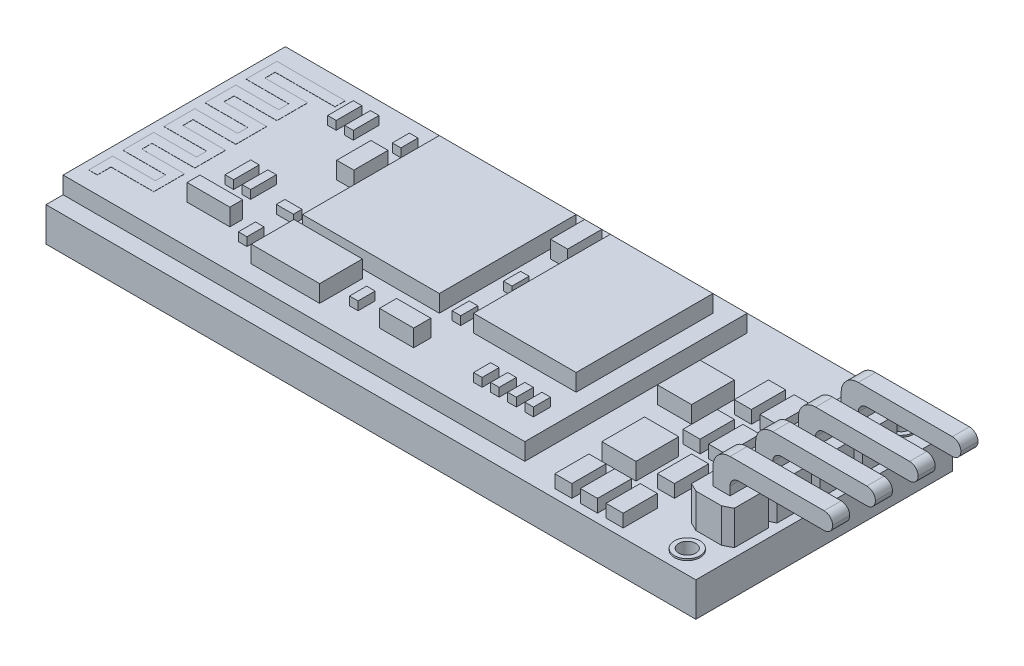
SolidWorks part; units mm, degrees
ref_plane "Alzado" through (0, 0, 0) normal (0, 0, 1) x (1, 0, 0)
ref_plane "Planta" through (0, 0, 0) normal (0, 1, 0) x (1, 0, 0)
ref_plane "Vista lateral" through (0, 0, 0) normal (1, 0, 0) x (0, 0, -1)
sketch "Croquis1" plane through (0, 0, 0) normal (0, 1, 0) x (1, 0, 0)
  line L0 (0, 0) -> (0, 7.5) construction
  line L1 (0, 0) -> (0, -7.5) construction
  line L2 (0, 0) -> (19, 0) construction
  line L3 (0, 0) -> (-19, 0) construction
  line L4 (-19, 0) -> (-19, 7.5) construction
  line L5 (-19, 7.5) -> (-19, -7.5)
  line L6 (-19, -7.5) -> (19, -7.5)
  line L7 (19, -7.5) -> (19, 7.5)
  line L8 (19, 7.5) -> (-19, 7.5)
extrude "Saliente-Extruir1" add sketch "Croquis1" along normal blind 2
sketch "Croquis2" plane through (0, 2, 0) normal (0, 1, 0) x (1, 0, 0)
  line L0 (-19, 0) -> (-19, 6.5) construction
  line L1 (-19, 7.5) -> (-19, -7.5) construction
  line L2 (-19, 6.5) -> (-19, -6.5)
  line L3 (-19, 6.5) -> (8, 6.5)
  line L4 (8, 6.5) -> (8, -6.5)
  line L5 (8, -6.5) -> (-19, -6.5)
extrude "Saliente-Extruir2" add sketch "Croquis2" along normal blind 1
sketch "Croquis3" plane through (0, 2, 0) normal (0, 1, 0) x (1, 0, 0)
  line L0 (19, 0) -> (18.5, 0) construction
  line L1 (19, -7.5) -> (19, 7.5) construction
  line L2 (18.5, 0) -> (18.5, 5)
  line L3 (18.5, 5) -> (16, 5)
  line L4 (16, 5) -> (16, -5)
  line L5 (16, -5) -> (18.5, -5)
  line L6 (18.5, -5) -> (18.5, 0)
  line L7 (18.5, 0) -> (18.52, -0.0603)
extrude "Saliente-Extruir3" add sketch "Croquis3" along normal blind 2 contours L5 L6 L2 L3 L4 region at (17.25, 2, 0)
sketch "Croquis4" plane through (0, 4, 0) normal (0, 1, 0) x (1, 0, 0)
  line L0 (16, 0) -> (16.5, 0) construction
  line L1 (18.5, 0) -> (18, 0) construction
  line L2 (18.5, 5) -> (18.5, 2.5) construction
  line L3 (18.5, 2.5) -> (16, 2.5) construction
  line L4 (16, -5) -> (18.5, -5)
  line L5 (18.5, -5) -> (18.5, 5)
  line L6 (18.5, 5) -> (16, 5)
  line L7 (16, 5) -> (16, -5)
  line L8 (16, -5) -> (18.5, -5)
  line L9 (18.5, -5) -> (18.5, 5)
  line L10 (18.5, 5) -> (16, 5)
  line L11 (16, 5) -> (16, -5)
  line L12 (18.5, -2.5) -> (16, -2.5) construction
  line L13 (16.5, 0) -> (18, 0)
  line L14 (16.5, -2.5) -> (16.5, 2.5) construction
  line L15 (16.5, 2.5) -> (16.5, 5) construction
  line L16 (18, -2.5) -> (18, 2.5) construction
  line L17 (18, 2.5) -> (18, 5) construction
  line L18 (18, -2.5) -> (18, -5) construction
  line L19 (16.5, -2.5) -> (16.5, -5) construction
  line L20 (16.5, 3.75) -> (18, 3.75) construction
  line L21 (17.25, 3.75) -> (17.25, 2.75) construction
  line L22 (17.25, 2.75) -> (18, 2.75) construction
  line L23 (17.25, 2.75) -> (16.5, 2.75) construction
  line L24 (17.25, 4.75) -> (18, 4.75) construction
  line L25 (17.25, 4.75) -> (16.5, 4.75) construction
  line L26 (17.25, 2.25) -> (18, 2.25) construction
  line L27 (17.25, 2.25) -> (16.5, 2.25) construction
  line L28 (17.25, 0.25) -> (18, 0.25) construction
  line L29 (17.25, 0.25) -> (16.5, 0.25) construction
  line L30 (17.25, -4.75) -> (16.5, -4.75) construction
  line L31 (17.25, -4.75) -> (18, -4.75) construction
  line L32 (17.25, -2.75) -> (18, -2.75) construction
  line L33 (17.25, -2.75) -> (16.5, -2.75) construction
  line L34 (17.25, -2.25) -> (16.5, -2.25) construction
  line L35 (17.25, -2.25) -> (18, -2.25) construction
  line L36 (17.25, -0.25) -> (18, -0.25) construction
  line L37 (17.25, -0.25) -> (16.5, -0.25) construction
  line L38 (16.5, -4.75) -> (16, -4.75) construction
  line L39 (16.5, -2.75) -> (16, -2.75) construction
  line L40 (18, -2.75) -> (18.5, -2.75) construction
  line L41 (18, -4.75) -> (18.5, -4.75) construction
  line L42 (16, -2.75) -> (16.5, -2.5)
  line L43 (18, -2.5) -> (16.5, -2.5)
  line L44 (18, -2.5) -> (18.5, -2.75)
  line L45 (18.5, -4.75) -> (18, -5)
  line L46 (16, -4.75) -> (16.5, -5)
  line L47 (16, -2.25) -> (16.5, -2.5)
  line L48 (18, -2.5) -> (18.5, -2.25)
  line L49 (18.5, -0.25) -> (18, 0)
  line L50 (16, -0.25) -> (16.5, 0)
  line L51 (16, 0.25) -> (16.5, 0)
  line L52 (18.5, 0.25) -> (18, 0)
  line L53 (18, 2.5) -> (18.5, 2.25)
  line L54 (16, 2.25) -> (16.5, 2.5)
  line L55 (16, 2.75) -> (16.5, 2.5)
  line L56 (18, 2.5) -> (16.5, 2.5)
  line L57 (18, 2.5) -> (18.5, 2.75)
  line L58 (18.5, 4.75) -> (18, 5)
  line L59 (16, 4.75) -> (16.5, 5)
  line M6 (16, -5) -> (18.5, -5)
  line M7 (18.5, -5) -> (18.5, 5)
  line M8 (18.5, 5) -> (16, 5)
  line M9 (16, 5) -> (16, -5)
  dimension "D1" = 0
extrude "Cortar-Extruir1" cut sketch "Croquis4" against normal blind 2 contours L59 M9 M8 | L58 L9 M8 | L57 L53 L9 | L55 L11 L54 | L9 L52 L49 | L51 L11 L50 | L48 L44 L9 | L47 L11 L42 | L45 L8 M7 | L46 M9 M6 region at (16.1667, 4, 4.9167) region at (18.3333, 4, 4.9167) region at (16.1667, 4, 2.5) region at (18.3333, 4, 2.5) region at (16.1667, 4, 0) region at (18.3333, 4, 0) region at (16.1667, 4, -2.5) region at (18.3333, 4, -2.5) region at (16.1667, 4, -4.9167) region at (18.3333, 4, -4.9167)
sketch "Croquis5" plane through (0, 2, 0) normal (0, 1, 0) x (1, 0, 0)
  line L0 (16, 0.25) -> (16, -0.25) construction
  line L1 (16, 0) -> (15, 0) construction
  line L2 (15, 0) -> (15, -7) construction
  line L3 (10, -7) -> (12.5, -7) construction
  line L4 (10, -7) -> (10, 6) construction
  line L5 (10, 6) -> (12.5, 6) construction
  line L6 (15, 6) -> (15, 0) construction
  line L7 (13.25, 0) -> (13, 0) construction
  line L8 (12.5, -7) -> (15, -7) construction
  line L9 (12.5, 6) -> (15, 6) construction
  line L10 (13.75, -7) -> (14.25, -7) construction
  line L11 (13.75, -7) -> (13.25, -7) construction
  line L12 (13.25, -7) -> (14.25, -7)
  line L13 (14.25, -7) -> (14.25, -5)
  line L14 (14.25, -5) -> (13.25, -5)
  line L15 (13.25, -5) -> (13.25, -7)
  line L16 (13.75, -5) -> (13.75, -4) construction
  line L17 (13.75, -4) -> (14.25, -4)
  line L18 (14.25, -4) -> (14.25, -2)
  line L19 (14.25, -2) -> (13.25, -2)
  line L20 (13.25, -2) -> (13.25, -4)
  line L21 (13.25, -4) -> (13.75, -4)
  line L22 (13.75, -2) -> (13.75, -1) construction
  line L23 (13.75, -1) -> (14.25, -1)
  line L24 (14.25, -1) -> (14.25, 1)
  line L25 (14.25, 1) -> (13.25, 1)
  line L26 (13.25, 1) -> (13.25, -1)
  line L27 (13.25, -1) -> (13.75, -1)
  line L28 (13.75, 1) -> (13.75, 2) construction
  line L29 (13.75, 2) -> (14.25, 2)
  line L30 (14.25, 2) -> (14.25, 4)
  line L31 (14.25, 4) -> (13.25, 4)
  line L32 (13.25, 4) -> (13.25, 2)
  line L33 (13.25, 2) -> (13.75, 2)
  line L34 (13, 0) -> (13, -7) construction
  line L35 (13, 0) -> (13, 6) construction
  line L36 (12.75, 4) -> (12.75, 2)
  line L37 (12.75, 2) -> (12.25, 2)
  line L38 (12.25, 2) -> (11.75, 2)
  line L39 (11.75, 2) -> (11.75, 4)
  line L40 (11.75, 4) -> (12.75, 4)
  line L41 (12.25, -1) -> (11.75, -1)
  line L42 (12.75, -1) -> (12.25, -1)
  line L43 (12.75, 1) -> (12.75, -1)
  line L44 (11.75, 1) -> (12.75, 1)
  line L45 (11.75, -1) -> (11.75, 1)
  line L46 (12.75, -5) -> (12.75, -7)
  line L47 (11.75, -5) -> (12.75, -5)
  line L48 (11.75, -7) -> (11.75, -5)
  line L49 (12.75, -7) -> (11.75, -7)
  line L50 (11.75, 0) -> (11.5, 0) construction
  line L51 (11.5, 0) -> (11.5, -7) construction
  line L52 (11.25, -7) -> (11.25, -5)
  line L53 (11.25, -5) -> (10.25, -5)
  line L54 (10.25, -5) -> (10.25, -7)
  line L55 (10.25, -7) -> (11.25, -7)
  line L56 (13.25, -3) -> (12.25, -3) construction
  line L57 (12.25, -3) -> (12.25, -4.25)
  line L58 (12.25, -4.25) -> (10.25, -4.25)
  line L59 (10.25, -4.25) -> (10.25, -1.75)
  line L60 (10.25, -1.75) -> (12.25, -1.75)
  line L61 (12.25, -1.75) -> (12.25, -3)
  line L62 (12.25, 2) -> (12.25, 1) construction
  line L63 (12.25, 1.5) -> (11, 1.5) construction
  line L64 (11, 1.5) -> (11, 0.25)
  line L65 (11, 1.5) -> (11, 2.75)
  line L66 (11, 0.25) -> (9, 0.25)
  line L67 (9, 0.25) -> (9, 2.75)
  line L68 (9, 2.75) -> (11, 2.75)
extrude "Saliente-Extruir4" add sketch "Croquis5" along normal blind 0.75
sketch "Croquis6" plane through (0, 2.75, 0) normal (0, 1, 0) x (1, 0, 0)
  line L4 (12.25, -4.25) -> (12.25, -1.75)
  line L5 (12.25, -1.75) -> (10.25, -1.75)
  line L6 (10.25, -1.75) -> (10.25, -4.25)
  line L7 (10.25, -4.25) -> (12.25, -4.25)
  line L8 (12.25, -4.25) -> (12.25, -1.75)
  line L9 (12.25, -1.75) -> (10.25, -1.75)
  line L10 (10.25, -1.75) -> (10.25, -4.25)
  line L11 (10.25, -4.25) -> (12.25, -4.25)
  dimension "D1" = 0
extrude "Saliente-Extruir5" add sketch "Croquis6" along normal blind 0.25
sketch "Croquis7" plane through (0, 2.75, 0) normal (0, 1, 0) x (1, 0, 0)
  line L4 (11, 0.25) -> (11, 2.75)
  line L5 (11, 2.75) -> (9, 2.75)
  line L6 (9, 2.75) -> (9, 0.25)
  line L7 (9, 0.25) -> (11, 0.25)
  line L8 (11, 0.25) -> (11, 2.75)
  line L9 (11, 2.75) -> (9, 2.75)
  line L10 (9, 2.75) -> (9, 0.25)
  line L11 (9, 0.25) -> (11, 0.25)
  dimension "D1" = 0
extrude "Saliente-Extruir6" add sketch "Croquis7" along normal blind 0.25
sketch "Croquis8" plane through (0, 4, 0) normal (0, 1, 0) x (1, 0, 0)
  line L0 (17.25, 2.5) -> (17.25, 5) construction
  line L2 (17.25, 0) -> (17.25, 2.5) construction
  line L3 (18, 5) -> (16.5, 5) construction
  line L4 (17.25, 0) -> (18, 0) construction
  line L5 (16.5, -2.5) -> (18, -2.5) construction
  line L6 (17.75, -4.25) -> (16.75, -4.25)
  line L7 (17.75, -4.25) -> (17.75, -3.25)
  line L8 (17.75, -3.25) -> (16.75, -3.25)
  line L9 (16.75, -4.25) -> (16.75, -3.25)
  line L10 (17.75, -4.25) -> (16.75, -3.25) construction
  line L11 (17.75, -3.25) -> (16.75, -4.25) construction
  line L12 (17.75, -0.75) -> (16.75, -0.75)
  line L13 (16.75, -0.75) -> (16.75, -1.75)
  line L14 (17.75, -1.75) -> (16.75, -1.75)
  line L15 (17.75, -0.75) -> (17.75, -1.75)
  line L16 (17.75, 1.75) -> (16.75, 1.75)
  line L17 (16.75, 0.75) -> (16.75, 1.75)
  line L18 (17.75, 0.75) -> (16.75, 0.75)
  line L19 (17.75, 0.75) -> (17.75, 1.75)
  line L20 (17.75, 4.25) -> (16.75, 4.25)
  line L21 (16.75, 4.25) -> (16.75, 3.25)
  line L22 (17.75, 3.25) -> (16.75, 3.25)
  line L23 (17.75, 4.25) -> (17.75, 3.25)
  circle A0 centre (17.25, 3.75) radius 0.5 construction
  circle A1 centre (17.25, 1.25) radius 0.5 construction
  circle A2 centre (17.25, -3.75) radius 0.5 construction
  circle A3 centre (17.25, -1.25) radius 0.5 construction
extrude "Saliente-Extruir8" add sketch "Croquis8" along normal blind 2
sketch "Croquis9" plane through (16.75, 0, 0) normal (-1, 0, 0) x (0, 0, 1)
  line L0 (3.25, 6) -> (4.25, 6)
  line L1 (4.25, 6) -> (4.25, 5)
  line L2 (4.25, 6) -> (4.25, 4) construction
  line L3 (4.25, 5) -> (3.25, 5)
  line L4 (3.25, 6) -> (3.25, 4) construction
  line L5 (3.25, 5) -> (3.25, 6)
  line L6 (1.75, 6) -> (1.75, 5)
  line L7 (1.75, 6) -> (1.75, 4) construction
  line L8 (1.75, 5) -> (0.75, 5)
  line L9 (0.75, 6) -> (0.75, 4) construction
  line L10 (0.75, 5) -> (0.75, 6)
  line L11 (0.75, 6) -> (1.75, 6)
  line L12 (-1.75, 6) -> (-0.75, 6)
  line L13 (-0.75, 6) -> (-0.75, 5)
  line L14 (-0.75, 6) -> (-0.75, 4) construction
  line L15 (-0.75, 5) -> (-1.75, 5)
  line L16 (-1.75, 6) -> (-1.75, 4) construction
  line L17 (-1.75, 5) -> (-1.75, 6)
  line L18 (-3.25, 6) -> (-3.25, 5)
  line L19 (-3.25, 6) -> (-3.25, 4) construction
  line L20 (-3.25, 5) -> (-4.25, 5)
  line L21 (-4.25, 6) -> (-4.25, 4) construction
  line L22 (-4.25, 5) -> (-4.25, 6)
  line L23 (-4.25, 6) -> (-3.25, 6)
extrude "Saliente-Extruir9" add sketch "Croquis9" against normal blind 7
fillet "Redondeo1" radius 0.5 1 edges at (17.75, 5, 3.75) type face fillet first side face at (17.75, 4.5, 3.75) second side face at (20.75, 5, 3.75)
fillet "Redondeo2" radius 0.5 1 edges at (17.75, 5, 1.25) type face fillet first side face at (17.75, 4.5, 1.25) second side face at (20.75, 5, 1.25)
fillet "Redondeo3" radius 0.5 1 edges at (17.75, 5, -1.25) type face fillet first side face at (17.75, 4.5, -1.25) second side face at (20.75, 5, -1.25)
fillet "Redondeo4" radius 0.5 1 edges at (17.75, 5, -3.75) type face fillet first side face at (17.75, 4.5, -3.75) second side face at (20.75, 5, -3.75)
fillet "Redondeo5" radius 1 1 edges at (16.75, 6, 3.75) type face fillet first side face at (16.75, 5, 3.75) second side face at (20.25, 6, 3.75)
fillet "Redondeo6" radius 1 1 edges at (16.75, 6, 1.25) type face fillet first side face at (16.75, 5, 1.25) second side face at (20.25, 6, 1.25)
fillet "Redondeo7" radius 1 1 edges at (16.75, 6, -1.25) type face fillet first side face at (16.75, 5, -1.25) second side face at (20.25, 6, -1.25)
fillet "Redondeo8" radius 1 1 edges at (16.75, 6, -3.75) type face fillet first side face at (16.75, 5, -3.75) second side face at (20.25, 6, -3.75)
sketch "Croquis10" plane through (0, 2, 0) normal (0, 1, 0) x (1, 0, 0)
  line L0 (17.25, -5) -> (17.25, -7.5) construction
  line L1 (16.5, -5) -> (18, -5) construction
  line L2 (-19, -7.5) -> (19, -7.5) construction
  line L3 (17.25, 5) -> (17.25, 7.5) construction
  line L4 (18, 5) -> (16.5, 5) construction
  line L5 (19, 7.5) -> (-19, 7.5) construction
  circle A0 centre (17.25, -6.25) radius 0.5
  circle A1 centre (17.25, 6.25) radius 0.5
  circle A2 centre (17.25, -6.25) radius 0.75
  circle A3 centre (17.25, 6.25) radius 0.75
extrude "Saliente-Extruir10" add sketch "Croquis10" along normal blind 0.1 and the other way blind 2.1
sketch "Croquis11" plane through (0, 2, 0) normal (0, 1, 0) x (1, 0, 0)
  circle A1 centre (17.25, 6.25) radius 0.5
  circle A2 centre (17.25, 6.25) radius 0.5
  dimension "D1" = 0
extrude "Cortar-Extruir2" cut sketch "Croquis11" against normal blind 2
sketch "Croquis12" plane through (0, 2, 0) normal (0, 1, 0) x (1, 0, 0)
  circle A1 centre (17.25, -6.25) radius 0.5
  circle A2 centre (17.25, -6.25) radius 0.5
  dimension "D1" = 0
extrude "Cortar-Extruir3" cut sketch "Croquis12" against normal blind 2
sketch "Croquis13" plane through (0, 3, 0) normal (0, 1, 0) x (1, 0, 0)
  line L3 (-9, 5.5) -> (-9, -2.5)
  line L4 (-9, -2.5) -> (-1, -2.5)
  line L5 (-1, -2.5) -> (-1, 5.5)
  line L6 (-1, 5.5) -> (-9, 5.5)
  line L7 (0, -4) -> (0, -5)
  line L8 (1, 1.5) -> (1, 5.5)
  line L9 (1, 5.5) -> (7, 5.5)
  line L10 (7, 5.5) -> (7, -2.5)
  line L11 (7, -2.5) -> (1, -2.5)
  line L12 (1, -2.5) -> (1, 1.5)
  line L19 (0, -5) -> (-2, -5)
  line L20 (-2, -5) -> (-2, -4)
  line L21 (-2, -4) -> (0, -4)
extrude "Saliente-Extruir11" add sketch "Croquis13" along normal blind 1
sketch "Croquis14" plane through (0, 3, 0) normal (0, 1, 0) x (1, 0, 0)
  line L0 (-19, 0) -> (-18.5, 0) construction
  line L1 (-19, 6.5) -> (-19, -6.5) construction
  line L2 (-18.5, 0) -> (-18.5, 6.5) construction
  line L3 (8, 6.5) -> (-19, 6.5) construction
  line L4 (-18.5, 0) -> (-18.5, -6.5) construction
  line L5 (-19, -6.5) -> (8, -6.5) construction
  line L6 (-19, 6.5) -> (-19, 5.5) construction
  line L7 (-19, 5.5) -> (-18.5, 5.5) construction
  line L8 (-18.5, 5.5) -> (-14.5, 5.5)
  line L9 (-14.5, 5.5) -> (-14.5, 4.9)
  line L10 (-14.5, 4.9) -> (-18, 4.9)
  line L11 (-18, 4.9) -> (-18, 4.3)
  line L12 (-18, 4.3) -> (-15.5, 4.3)
  line L13 (-15.5, 4.3) -> (-15.5, 2.5)
  line L14 (-15.5, 2.5) -> (-18, 2.5)
  line L15 (-18, 2.5) -> (-18, 1.9)
  line L16 (-18, 1.9) -> (-15.5, 1.9)
  line L17 (-15.5, 1.9) -> (-15.5, 0.1)
  line L18 (-18.5, 5.5) -> (-18.5, 3.7)
  line L19 (-18.5, 3.7) -> (-16, 3.7)
  line L20 (-16, 3.7) -> (-16, 3.1)
  line L21 (-16, 3.1) -> (-18.5, 3.1)
  line L22 (-18.5, 3.1) -> (-18.5, 1.3)
  line L23 (-18.5, 1.3) -> (-16, 1.3)
  line L24 (-16, 0.7) -> (-18.5, 0.7)
  line L25 (-16, 1.3) -> (-16, 0.7)
  line L26 (-18.5, 0.7) -> (-18.5, -1.1)
  line L27 (-15.5, 0.1) -> (-18, 0.1)
  line L28 (-18, 0.1) -> (-18, -0.5)
  line L29 (-18, -0.5) -> (-15.5, -0.5)
  line L30 (-15.5, -0.5) -> (-15.5, -2.3)
  line L31 (-18.5, -1.1) -> (-16, -1.1)
  line L32 (-16, -1.1) -> (-16, -1.7)
  line L33 (-16, -1.7) -> (-18.5, -1.7)
  line L34 (-15.5, -2.3) -> (-18, -2.3)
  line L35 (-18, -2.3) -> (-18, -2.9)
  line L36 (-18, -2.9) -> (-15.5, -2.9)
  line L37 (-18.5, -1.7) -> (-18.5, -3.5)
  line L38 (-18.5, -3.5) -> (-16, -3.5)
  line L39 (-16, -3.5) -> (-16, -4.1)
  line L40 (-18.5, -6.5) -> (-18.5, -5.5) construction
  line L41 (-15.5, -2.9) -> (-15.5, -4.7)
  line L42 (-15.5, -4.7) -> (-18, -4.7)
  line L43 (-18, -4.7) -> (-18, -5.5)
  line L44 (-16, -4.1) -> (-18.5, -4.1)
  line L45 (-18.5, -4.1) -> (-18.5, -5.5)
  line L46 (-18, -5.5) -> (-18.5, -5.5)
extrude "Saliente-Extruir12" add sketch "Croquis14" along normal blind 0.01
sketch "Croquis15" plane through (0, 3, 0) normal (0, 1, 0) x (1, 0, 0)
  line L0 (-10.25, 4.25) -> (-10.25, 3.25) construction
  line L1 (-10.25, -2.25) -> (-9.7803, -2.25) construction
  line L2 (7, -4) -> (7, -5)
  line L3 (7, -5) -> (7.0244, -5.0141)
  line L4 (7, -4) -> (6.5, -4)
  line L5 (6.5, -4) -> (6.5, -5)
  line L6 (6.5, -5) -> (7, -5)
  line L7 (-9.7803, -2.25) -> (-10.7803, -2.25)
  line L8 (-1, -2.5) -> (1, -2.5) construction
  line L9 (-10.7803, -2.25) -> (-10.7803, -1.75)
  line L10 (5.5, -4) -> (6, -4)
  line L11 (5.5, -4) -> (5.5, -5)
  line L12 (6, -5) -> (5.5, -5)
  line L13 (6, -4) -> (6, -5)
  line L14 (0, -1.5) -> (0.25, -1.5) construction
  line L15 (0.25, -1.5) -> (-0.25, -1.5)
  line L16 (5, -4) -> (5, -5)
  line L17 (5, -4) -> (4.5, -4)
  line L18 (4.5, -4) -> (4.5, -5)
  line L19 (4.5, -5) -> (5, -5)
  line L20 (4, -5) -> (3.5, -5)
  line L21 (4, -4) -> (4, -5)
  line L22 (3.5, -4) -> (4, -4)
  line L23 (3.5, -4) -> (3.5, -5)
  line L24 (-0.25, -1.5) -> (-0.25, -2.5)
  line L25 (-0.25, -2.5) -> (0.25, -2.5)
  line L26 (0.25, -2.5) -> (0.25, -1.5)
  line L27 (0, 1.5) -> (0, 3.5) construction
  line L28 (0, 3.5) -> (0.5, 3.5)
  line L29 (-0.25, 1.5) -> (0.25, 1.5)
  line L30 (-0.25, 0.5) -> (-0.25, 1.5)
  line L31 (0.25, 0.5) -> (-0.25, 0.5)
  line L32 (0.25, 1.5) -> (0.25, 0.5)
  line L33 (0.5, 3.5) -> (0.5, 5.5)
  line L34 (0.5, 5.5) -> (-0.5, 5.5)
  line L35 (-0.5, 5.5) -> (-0.5, 3.5)
  line L36 (-0.5, 3.5) -> (0, 3.5)
  line L37 (-9, -2.5) -> (-9, -6.5) construction
  line L38 (-19, -6.5) -> (8, -6.5) construction
  line L39 (-5, -2.5) -> (-5, -3) construction
  line L40 (-9, -2.5) -> (-1, -2.5) construction
  line L41 (-5, -3) -> (-5, -5.5)
  line L42 (-5, -3) -> (-9, -3)
  line L43 (-9, -3) -> (-9, -5.5)
  line L44 (-9, -5.5) -> (-5, -5.5)
  line L45 (-10.7803, -1.75) -> (-9.7803, -1.75)
  line L46 (-4, -4.25) -> (-4, -4.75) construction
  line L47 (-4, -4.75) -> (-4, -3.75)
  line L48 (-4, -3.75) -> (-3.5, -3.75)
  line L49 (-3.5, -3.75) -> (-3.5, -4.75)
  line L50 (-3.5, -4.75) -> (-4, -4.75)
  line L51 (-7, -3) -> (-7, -5.5) construction
  line L52 (-10.5, -4.75) -> (-10, -4.75)
  line L53 (-10, -4.75) -> (-10, -3.75)
  line L54 (-10, -3.75) -> (-10.5, -3.75)
  line L55 (-10.5, -3.75) -> (-10.5, -4.75)
  line L56 (-12.2803, -2.25) -> (-12.2803, -0.75)
  line L57 (-9.7803, -1.75) -> (-9.7803, -2.25)
  line L58 (-12.2803, -0.75) -> (-12.7803, -0.75)
  line L59 (-12.7803, -0.75) -> (-12.7803, -2.25)
  line L60 (-12.7803, -2.25) -> (-12.2803, -2.25)
  line L61 (-13.7803, 5.25) -> (-13.2803, 5.25)
  line L62 (-13.2803, -2.25) -> (-13.2803, -0.75)
  line L63 (-13.2803, -0.75) -> (-13.7803, -0.75)
  line L64 (-13.7803, -0.75) -> (-13.7803, -2.25)
  line L65 (-13.7803, -2.25) -> (-13.2803, -2.25)
  line L66 (-13.7803, 3.75) -> (-13.7803, 5.25)
  line L68 (-10.25, 3.25) -> (-9.75, 3.25)
  line L69 (-13.2803, 3.75) -> (-13.7803, 3.75)
  line L70 (-13.2803, 5.25) -> (-13.2803, 3.75)
  line L71 (-12.7803, 5.25) -> (-12.2803, 5.25)
  line L72 (-12.7803, 3.75) -> (-12.7803, 5.25)
  line L73 (-12.2803, 3.75) -> (-12.7803, 3.75)
  line L74 (-12.2803, 5.25) -> (-12.2803, 3.75)
  line L75 (-9.75, 3.25) -> (-9.75, 1.25)
  line L76 (-9.75, 1.25) -> (-10.75, 1.25)
  line L77 (-10.5, 4.25) -> (-10.5, 5.25)
  line L78 (-10, 4.25) -> (-10.5, 4.25)
  line L79 (-10, 5.25) -> (-10, 4.25)
  line L80 (-10.5, 5.25) -> (-10, 5.25)
  line L81 (-10.75, 1.25) -> (-10.75, 3.25)
  line L82 (-10.75, 3.25) -> (-10.25, 3.25)
extrude "Saliente-Extruir13" add sketch "Croquis15" along normal blind 0.5 contours L59 L60 L56 L58 | L57 L45 L9 L7 | L82 L81 L76 L75 L68 | L43 L44 L41 L42 | L50 L49 L48 L47 | L25 L26 L15 L24 | L32 L29 L30 L31 | L35 L36 L28 L33 L34 | L22 L23 L20 L21 | L18 L19 L16 L17 | L13 L10 L11 L12 | L5 L6 L2 L4 | L66 L61 L70 L69 | L74 L73 L72 L71 | L77 L80 L79 L78 | L62 L63 L64 L65 | L53 L54 L55 L52 region at (6.75, 3, 4.5) region at (-10.2803, 3, 2) region at (5.75, 3, 4.5) region at (0, 3, 2) region at (4.75, 3, 4.5) region at (3.75, 3, 4.5) region at (0, 3, -4.5) region at (0, 3, -1) region at (-7, 3, 4.25) region at (-3.75, 3, 4.25) region at (-12.5303, 3, 1.5) region at (-10.25, 3, -2.25)
sketch "Croquis17" plane through (0, 3, 0) normal (0, 1, 0) x (1, 0, 0)
  line L0 (-10.5, -4.25) -> (-11.5, -4.25) construction
  line L1 (-10.5, -3.75) -> (-10.5, -4.75) construction
  line L2 (-11.5, -4.25) -> (-11.5, -3.5)
  line L3 (-11.5, -3.5) -> (-14, -3.5)
  line L4 (-14, -3.5) -> (-14, -4.25)
  line L5 (-14, -4.25) -> (-11.5, -4.25)
extrude "Saliente-Extruir14" add sketch "Croquis17" along normal blind 1
sketch "Croquis18" plane through (0, 3.5, 0) normal (0, 1, 0) x (1, 0, 0)
  line L4 (-9.75, 3.25) -> (-10.75, 3.25)
  line L5 (-10.75, 3.25) -> (-10.75, 1.25)
  line L6 (-10.75, 1.25) -> (-9.75, 1.25)
  line L7 (-9.75, 1.25) -> (-9.75, 3.25)
  line L8 (-9.75, 3.25) -> (-10.75, 3.25)
  line L9 (-10.75, 3.25) -> (-10.75, 1.25)
  line L10 (-10.75, 1.25) -> (-9.75, 1.25)
  line L11 (-9.75, 1.25) -> (-9.75, 3.25)
  dimension "D1" = 0
extrude "Saliente-Extruir15" add sketch "Croquis18" along normal blind 0.5
sketch "Croquis19" plane through (0, 3.5, 0) normal (0, 1, 0) x (1, 0, 0)
  line L4 (-9, -3) -> (-9, -5.5)
  line L5 (-9, -5.5) -> (-5, -5.5)
  line L6 (-5, -5.5) -> (-5, -3)
  line L7 (-5, -3) -> (-9, -3)
  line L8 (-9, -3) -> (-9, -5.5)
  line L9 (-9, -5.5) -> (-5, -5.5)
  line L10 (-5, -5.5) -> (-5, -3)
  line L11 (-5, -3) -> (-9, -3)
  dimension "D1" = 0
extrude "Saliente-Extruir16" add sketch "Croquis19" along normal blind 0.5
sketch "Croquis21" plane through (0, 3.5, 0) normal (0, 1, 0) x (1, 0, 0)
  line L4 (-0.5, 5.5) -> (-0.5, 3.5)
  line L5 (-0.5, 3.5) -> (0.5, 3.5)
  line L6 (0.5, 3.5) -> (0.5, 5.5)
  line L7 (0.5, 5.5) -> (-0.5, 5.5)
  line L8 (-0.5, 5.5) -> (-0.5, 3.5)
  line L9 (-0.5, 3.5) -> (0.5, 3.5)
  line L10 (0.5, 3.5) -> (0.5, 5.5)
  line L11 (0.5, 5.5) -> (-0.5, 5.5)
  dimension "D1" = 0
extrude "Saliente-Extruir17" add sketch "Croquis21" along normal blind 0.5
fillet "Redondeo9" radius 0.5 1 edges at (23.75, 6, 3.75) type face fillet first side face at (20.75, 6, 3.75) second side face at (23.75, 5.5, 3.75)
fillet "Redondeo12" radius 0.5 1 edges at (23.75, 5, 3.75) type face fillet first side face at (23.75, 5.25, 3.75) second side face at (21, 5, 3.75)
fillet "Redondeo13" radius 0.5 1 edges at (23.75, 6, 1.25) type face fillet first side face at (20.75, 6, 1.25) second side face at (23.75, 5.5, 1.25)
fillet "Redondeo14" radius 0.5 1 edges at (23.75, 5, 1.25) type face fillet first side face at (21, 5, 1.25) second side face at (23.75, 5.25, 1.25)
fillet "Redondeo15" radius 0.5 1 edges at (23.75, 6, -1.25) type face fillet first side face at (20.75, 6, -1.25) second side face at (23.75, 5.5, -1.25)
fillet "Redondeo16" radius 0.5 1 edges at (23.75, 5, -1.25) type face fillet first side face at (21, 5, -1.25) second side face at (23.75, 5.25, -1.25)
fillet "Redondeo17" radius 0.5 1 edges at (23.75, 6, -3.75) type face fillet first side face at (20.75, 6, -3.75) second side face at (23.75, 5.5, -3.75)
fillet "Redondeo18" radius 0.5 1 edges at (23.75, 5, -3.75) type face fillet first side face at (21, 5, -3.75) second side face at (23.75, 5.25, -3.75)
